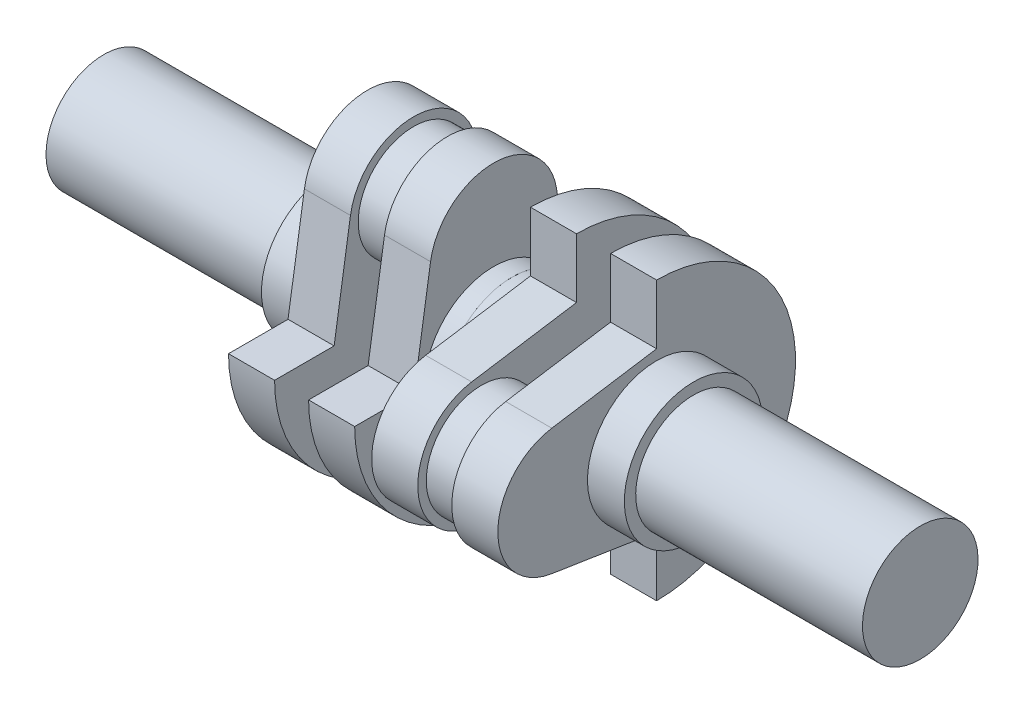
SolidWorks part; units mm, degrees
ref_plane "Front Plane" through (0, 0, 0) normal (0, 0, 1) x (1, 0, 0)
ref_plane "Top Plane" through (0, 0, 0) normal (0, 1, 0) x (1, 0, 0)
ref_plane "Right Plane" through (0, 0, 0) normal (1, 0, 0) x (0, 0, -1)
sketch "Sketch1" plane through (0, 0, 0) normal (1, 0, 0) x (0, 0, -1)
  circle A0 centre (0, 0) radius 38.6953
  dimension "D1" = 77.3906
extrude "Boss-Extrude1" add sketch "Sketch1" along normal blind 20.6375
sketch "Sketch2" plane through (20.6375, 0, 0) normal (1, 0, 0) x (0, 0, -1)
  circle A0 centre (0, 0) radius 90.4875
  dimension "D1" = 180.975
extrude "Boss-Extrude2" add sketch "Sketch2" along normal blind 25.7969
sketch "Sketch3" plane through (46.4344, 0, 0) normal (1, 0, 0) x (0, 0, -1)
  circle A0 centre (0, 53.1812) radius 30.9562
  circle A1 centre (0, 0) radius 90.4875 construction
  dimension "D1" = 53.1812
  dimension "D2" = 61.9125
extrude "Boss-Extrude3" add sketch "Sketch3" along normal blind 9.525
sketch "Sketch5" plane through (46.4344, 0, 0) normal (1, 0, 0) x (0, 0, -1)
  line L0 (-77.7875, 0) -> (-44.45, 0)
  line L1 (-44.45, 0) -> (-35.2916, 58.6885)
  line L2 (0, 0) -> (0, -50.2532) construction
  line L3 (44.45, 0) -> (35.2916, 58.6885)
  line L4 (77.7875, 0) -> (44.45, 0)
  arc A0 (35.2916, 58.6885) -> (-35.2916, 58.6885) centre (0, 53.1812) ccw
  circle A3 centre (0, 53.1812) radius 30.9562 construction
  arc A6 (-77.7875, 0) -> (77.7875, 0) centre (0, 0) ccw
  circle A8 centre (0, 0) radius 90.4875
  circle A9 centre (0, 0) radius 90.4875 construction
  circle A10 centre (0, 0) radius 88.9 construction
  circle M2 centre (0, 0) radius 90.4875
  dimension "D2" = 155.575
  dimension "D3" = 44.45
  dimension "D1" = 177.8
extrude "Cut-Extrude1" cut sketch "Sketch5" against normal through all contours A6 L0 L1 A0 L3 L4 M2 region at (46.4344, 0, 87.9281)
mirror "Mirror1" about plane through (55.9594, 53.1812, 0) normal (1, 0, 0) of bodies 104 118
sketch "Sketch8" plane through (0, 0, 0) normal (-1, 0, 0) x (0, 0, 1)
  circle A2 centre (0, 0) radius 32.3453
  circle A6 centre (0, 0) radius 32.3453
  dimension "D1" = 6.35
extrude "Boss-Extrude5" add sketch "Sketch8" along normal blind 127
ref_plane "Plane2" through (55.9594, 0, 0) normal (1, 0, 0) x (0, 0, -1)
sketch "Sketch9" plane through (91.2812, 0, 0) normal (1, 0, 0) x (0, 0, -1)
  line L2 (-35.2916, 58.6885) -> (-44.45, 0)
  line L4 (-35.2916, 58.6885) -> (-44.45, 0)
  line L5 (44.45, 0) -> (35.2916, 58.6885)
  line L6 (44.45, 0) -> (35.2916, 58.6885)
  line L13 (-44.45, 0) -> (-77.7875, 0)
  line L14 (-44.45, 0) -> (-77.7875, 0)
  line L15 (77.7875, 0) -> (44.45, 0)
  line L16 (77.7875, 0) -> (44.45, 0)
  arc A2 (35.2916, 58.6885) -> (-35.2916, 58.6885) centre (0, 53.1812) ccw
  arc A3 (-77.7875, 0) -> (77.7875, 0) centre (0, 0) ccw
  arc A6 (35.2916, 58.6885) -> (-35.2916, 58.6885) centre (0, 53.1812) ccw
  arc A8 (-77.7875, 0) -> (77.7875, 0) centre (0, 0) ccw
  dimension "D1" = 0
extrude "Cut-Extrude2" cut sketch "Sketch9" along normal through all
sketch "Sketch10" plane through (91.2812, 0, 0) normal (1, 0, 0) x (0, 0, -1)
  circle A0 centre (0, 0) radius 38.6953 construction
  circle A1 centre (0, 0) radius 38.6953
extrude "Boss-Extrude6" add sketch "Sketch10" along normal blind 10.3187
mirror "Mirror4" about plane through (101.6, 0, 0) normal (1, 0, 0) of bodies 115
move or copy body "Body-Move/Copy3" bodies to move or copy 116 copy no rotation origin (0, 0, 0) rotation axis (1, 0, 0) rotation angle 90
ref_plane "Plane3" through (55.9594, 0, 0) normal (1, 0, 0) x (0, 0, -1)
ref_plane "Plane4" through (147.2406, 0, 0) normal (-1, 0, 0) x (0, 0, 1)
ref_axis "Axis1" through (330.2, 0, 0) along (-1, 0, 0)
